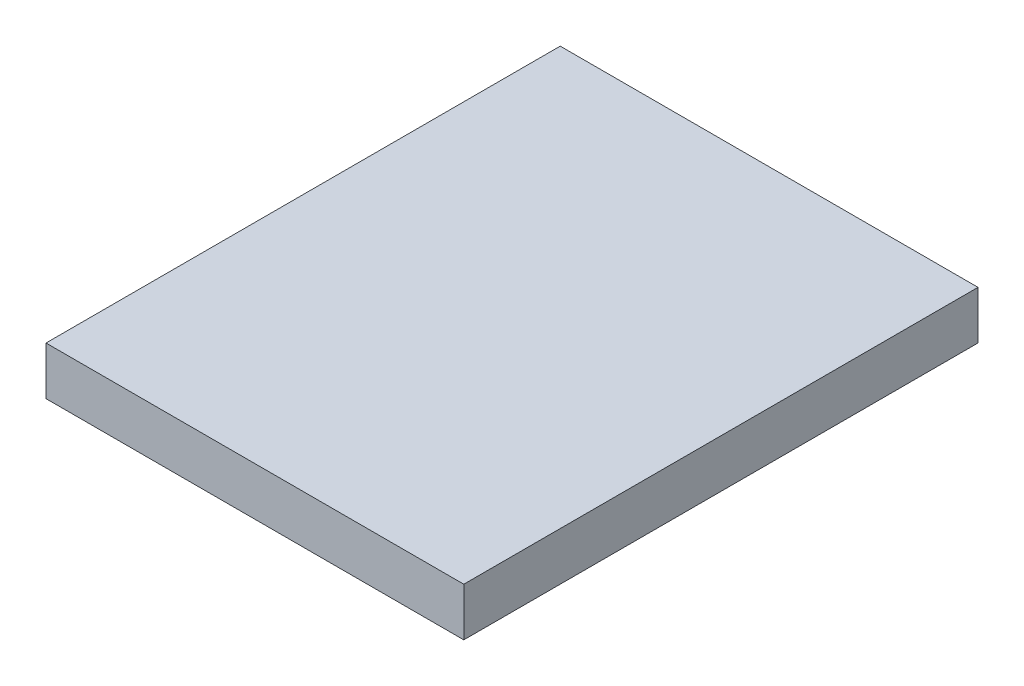
SolidWorks part; units mm, degrees
ref_plane "Front Plane" through (0, 0, 0) normal (0, 0, 1) x (1, 0, 0)
ref_plane "Top Plane" through (0, 0, 0) normal (0, 1, 0) x (1, 0, 0)
ref_plane "Right Plane" through (0, 0, 0) normal (1, 0, 0) x (0, 0, -1)
sketch "Sketch1" plane through (0, 0, 0) normal (0, 1, 0) x (1, 0, 0)
  line L1 (-73.1886, 49.3433) -> (91.9114, 49.3433)
  line L2 (-73.1886, 49.3433) -> (-73.1886, -153.8567)
  line L3 (-73.1886, -153.8567) -> (91.9114, -153.8567)
  line L4 (91.9114, 49.3433) -> (91.9114, -153.8567)
  line L5 (-73.1886, 49.3433) -> (91.9114, -153.8567) construction
  line L6 (-73.1886, -153.8567) -> (91.9114, 49.3433) construction
  point P0 (9.3614, -52.2567)
extrude "Boss-Extrude1" add sketch "Sketch1" along normal blind 19.05 contours L2 L1 L4 L3
